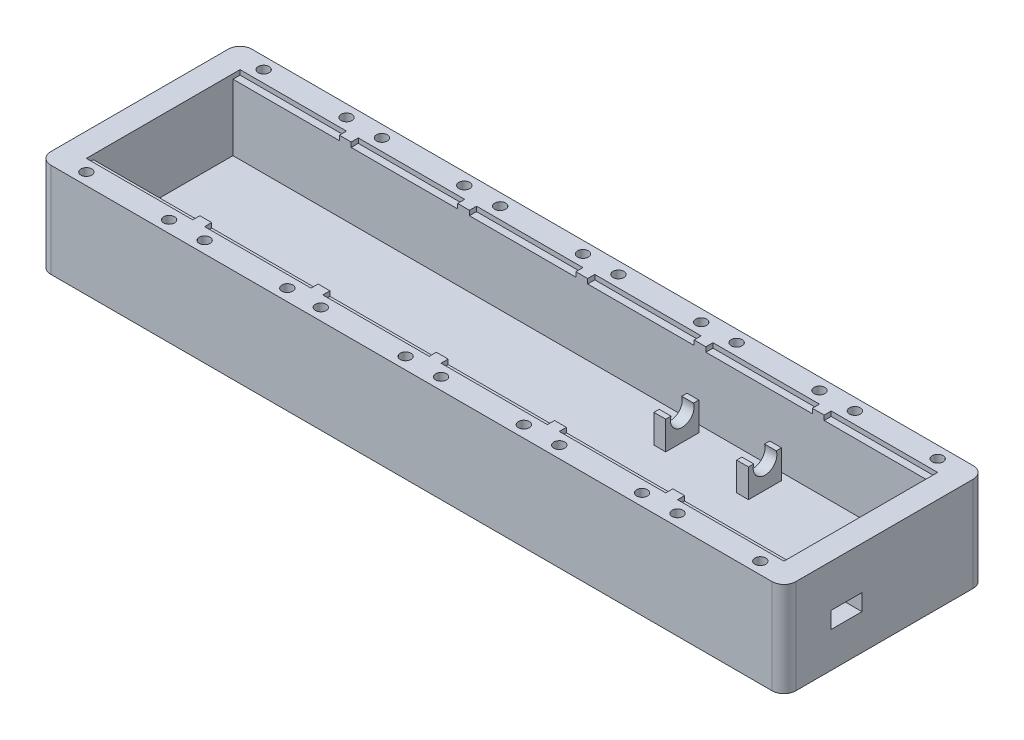
SolidWorks part; units mm, degrees
material "Starkstromplatine"
ref_plane "Ebene vorne" through (0, 0, 0) normal (0, 0, 1) x (1, 0, 0)
ref_plane "Ebene oben" through (0, 0, 0) normal (0, 1, 0) x (1, 0, 0)
ref_plane "Ebene rechts" through (0, 0, 0) normal (1, 0, 0) x (0, 0, -1)
sketch "Skizze2" plane through (0, 0, 0) normal (0, 0, 1) x (1, 0, 0)
  line L1 (0, 0) -> (315, 0)
  line L2 (0, 0) -> (0, 40)
  line L3 (0, 40) -> (315, 40)
  line L4 (315, 0) -> (315, 40)
  dimension "D1" = 315
  dimension "D2" = 40
extrude "Aufsatz-Linear austragen1" add sketch "Skizze2" along normal blind 85
sketch "Skizze4" plane through (0, 40, 0) normal (0, 1, 0) x (1, 0, 0)
  line L1 (10, -13) -> (305, -13)
  line L2 (10, -13) -> (10, -72)
  line L3 (10, -72) -> (305, -72)
  line L4 (305, -13) -> (305, -72)
  line L6 (0, -85) -> (0, 0) construction
  line L7 (315, -85) -> (315, 0) construction
  line L8 (315, -85) -> (0, -85) construction
  dimension "D1" = 59
  dimension "D2" = 13
  dimension "D3" = 10
  dimension "D4" = 10
extrude "Schnitt-Linear austragen1" cut sketch "Skizze4" against normal blind 30
sketch "Skizze11" plane through (0, 40, 0) normal (0, 1, 0) x (1, 0, 0)
  line L0 (10, -72) -> (305, -72) construction
  line L1 (10, -13) -> (55, -13)
  line L2 (10, -13) -> (10, -10)
  line L3 (10, -10) -> (55, -10)
  line L4 (55, -13) -> (55, -10)
  line L5 (55, -72) -> (10, -72)
  line L6 (55, -72) -> (55, -75)
  line L7 (55, -75) -> (10, -75)
  line L8 (10, -72) -> (10, -75)
  line L9 (305, -13) -> (10, -13) construction
  line L10 (60, -75) -> (105, -75)
  line L11 (60, -75) -> (60, -72)
  line L12 (60, -72) -> (105, -72)
  line L13 (105, -75) -> (105, -72)
  line L14 (110, -75.0087) -> (155, -75.0087)
  line L15 (110, -75.0087) -> (110, -72)
  line L16 (110, -72) -> (155, -72)
  line L17 (155, -75.0087) -> (155, -72)
  line L18 (160, -75.0087) -> (205, -75.0087)
  line L19 (160, -75.0087) -> (160, -72)
  line L20 (160, -72) -> (205, -72)
  line L21 (205, -75.0087) -> (205, -72)
  line L22 (210, -75) -> (255, -75)
  line L23 (210, -75) -> (210, -72)
  line L24 (210, -72) -> (255, -72)
  line L25 (255, -75) -> (255, -72)
  line L26 (260, -75) -> (305, -75)
  line L27 (260, -75) -> (260, -72)
  line L28 (260, -72) -> (305, -72)
  line L29 (305, -75) -> (305, -72)
  line L30 (305, -13) -> (260, -13)
  line L31 (305, -13) -> (305, -10)
  line L32 (305, -10) -> (260, -10)
  line L33 (260, -13) -> (260, -10)
  line L35 (255, -13) -> (210, -13)
  line L36 (255, -13) -> (255, -10)
  line L37 (255, -10) -> (210, -10)
  line L38 (210, -13) -> (210, -10)
  line L39 (205, -13) -> (160, -13)
  line L40 (205, -13) -> (205, -10)
  line L41 (205, -10) -> (160, -10)
  line L42 (160, -13) -> (160, -10)
  line L43 (155, -13) -> (110, -13)
  line L44 (155, -13) -> (155, -10)
  line L45 (155, -10) -> (110, -10)
  line L46 (110, -13) -> (110, -10)
  line L47 (105, -13) -> (60, -13)
  line L48 (105, -13) -> (105, -10)
  line L49 (105, -10) -> (60, -10)
  line L50 (60, -13) -> (60, -10)
  dimension "D1" = 45
  dimension "D2" = 3
  dimension "D3" = 45
  dimension "D4" = 5
  dimension "D5" = 5
  dimension "D6" = 5
  dimension "D7" = 5
  dimension "D8" = 5
  dimension "D9" = 5
  dimension "D10" = 45
  dimension "D11" = 45
  dimension "D12" = 45
  dimension "D13" = 45
  dimension "D14" = 45
  dimension "D15" = 5
  dimension "D16" = 5
  dimension "D17" = 5
  dimension "D18" = 5
  dimension "D19" = 45
  dimension "D20" = 45
  dimension "D21" = 45
  dimension "D22" = 45
  dimension "D23" = 3
  dimension "D24" = 3
  dimension "D25" = 3
  dimension "D26" = 3
  dimension "D27" = 3
  dimension "D28" = 3
  dimension "D29" = 3
  dimension "D30" = 3
extrude "Schnitt-Linear austragen4" cut sketch "Skizze11" against normal blind 2
sketch "Skizze17" plane through (0, 40, 0) normal (0, 1, 0) x (1, 0, 0)
  line L0 (55, -75) -> (55, -72) construction
  line L1 (315, 0) -> (0, 0) construction
  line L2 (315, -85) -> (0, -85) construction
  line L3 (10, -72) -> (10, -75) construction
  line L4 (10, -10) -> (10, -75) construction
  line L5 (55, -13) -> (55, -10) construction
  line L6 (60, -72) -> (60, -75) construction
  line L7 (105, -75) -> (105, -72) construction
  line L8 (155, -75.0087) -> (155, -72) construction
  line L10 (160, -72) -> (160, -75.0087) construction
  line L11 (205, -75.0087) -> (205, -72) construction
  line L12 (305, -75) -> (305, -10) construction
  line L13 (260, -72) -> (260, -75) construction
  line L14 (255, -75) -> (255, -72) construction
  line L15 (210, -72) -> (210, -75) construction
  line L16 (60, -10) -> (60, -13) construction
  line L18 (110, -10) -> (110, -13) construction
  circle A0 centre (50, -80) radius 2.3
  circle A1 centre (15, -80) radius 2.3
  circle A2 centre (15, -5) radius 2.3
  circle A3 centre (50, -5) radius 2.3
  circle A4 centre (65, -5) radius 2.3
  circle A5 centre (99.8349, -5) radius 2.3
  circle A6 centre (65, -80) radius 2.3
  circle A7 centre (100, -80) radius 2.3
  circle A8 centre (114.1455, -80) radius 2.3
  circle A9 centre (150, -80) radius 2.3
  circle A10 centre (165, -80) radius 2.3
  circle A11 centre (200, -80) radius 2.3
  circle A12 centre (215, -80) radius 2.3
  circle A13 centre (250, -80) radius 2.3
  circle A14 centre (265, -80) radius 2.3
  circle A15 centre (300, -80) radius 2.3
  circle A16 centre (300, -5) radius 2.3
  circle A17 centre (265, -5) radius 2.3
  circle A18 centre (250, -5) radius 2.3
  circle A19 centre (215, -5) radius 2.3
  circle A20 centre (200, -5) radius 2.3
  circle A21 centre (165, -5) radius 2.3
  circle A22 centre (150, -5) radius 2.3
  circle A23 centre (115, -5) radius 2.3
  dimension "D1" = 4.6
  dimension "D2" = 4.6
  dimension "D3" = 4.6
  dimension "D4" = 4.6
  dimension "D5" = 5
  dimension "D6" = 5
  dimension "D7" = 5
  dimension "D8" = 5
  dimension "D10" = 5
  dimension "D11" = 5
  dimension "D12" = 5
  dimension "D13" = 4.6
  dimension "D14" = 4.6
  dimension "D15" = 4.6
  dimension "D16" = 4.6
  dimension "D17" = 4.6
  dimension "D18" = 4.6
  dimension "D19" = 4.6
  dimension "D20" = 4.6
  dimension "D21" = 4.6
  dimension "D22" = 4.6
  dimension "D23" = 5
  dimension "D25" = 5
  dimension "D26" = 5
  dimension "D27" = 5
  dimension "D28" = 5
  dimension "D29" = 5
  dimension "D30" = 5
  dimension "D31" = 5
  dimension "D32" = 5
  dimension "D33" = 5
  dimension "D34" = 5
  dimension "D35" = 5
  dimension "D36" = 5
  dimension "D37" = 5
  dimension "D38" = 5
  dimension "D39" = 5
  dimension "D40" = 5
  dimension "D41" = 5
  dimension "D42" = 5
  dimension "D43" = 4.6
  dimension "D44" = 4.6
  dimension "D45" = 4.6
  dimension "D46" = 4.6
  dimension "D47" = 4.6
  dimension "D48" = 4.6
  dimension "D49" = 4.6
  dimension "D50" = 4.6
  dimension "D51" = 4.6
  dimension "D52" = 4.6
  dimension "D53" = 5
  dimension "D54" = 5
  dimension "D55" = 5
  dimension "D9" = 5
  dimension "D24" = 5
extrude "Schnitt-Linear austragen6" cut sketch "Skizze17" against normal blind 4
fillet "Verrundung2" radius 5 1 edges at (0, 20, 85)
fillet "Verrundung3" radius 5 1 edges at (0, 20, 0)
fillet "Verrundung4" radius 5 1 edges at (315, 20, 0)
fillet "Verrundung6" radius 5 1 edges at (315, 20, 85)
sketch "Skizze18" plane through (305, 0, 0) normal (-1, 0, 0) x (0, 0, 1)
  line L0 (72, 10) -> (72, 38) construction
  line L1 (52, 22) -> (65, 22)
  line L2 (52, 22) -> (52, 15)
  line L3 (52, 15) -> (65, 15)
  line L4 (65, 22) -> (65, 15)
  line L5 (72, 10) -> (13, 10) construction
  dimension "D1" = 7
  dimension "D2" = 13
  dimension "D3" = 7
  dimension "D4" = 5
extrude "Schnitt-Linear austragen7" cut sketch "Skizze18" against normal blind 10
sketch "Skizze20" plane through (0, 10, 0) normal (0, 1, 0) x (1, 0, 0)
  line L0 (305, -13) -> (10, -13) construction
  line L1 (240, -16) -> (245, -16)
  line L2 (240, -16) -> (240, -30)
  line L3 (240, -30) -> (245, -30)
  line L4 (245, -16) -> (245, -30)
  line L5 (205, -16) -> (210, -16)
  line L6 (205, -16) -> (205, -30)
  line L7 (205, -30) -> (210, -30)
  line L8 (210, -16) -> (210, -30)
  line L9 (305, -72) -> (305, -13) construction
  dimension "D1" = 14
  dimension "D2" = 14
  dimension "D3" = 5
  dimension "D4" = 5
  dimension "D5" = 3
  dimension "D6" = 3
  dimension "D7" = 30
  dimension "D8" = 60
extrude "Aufsatz-Linear austragen2" add sketch "Skizze20" along normal blind 12
sketch "Skizze21" plane through (205, 0, 0) normal (-1, 0, 0) x (0, 0, 1)
  line L0 (16, 22) -> (16, 10) construction
  line L1 (16, 22) -> (30, 22) construction
  circle A0 centre (23, 20.5) radius 5
  dimension "D1" = 7
  dimension "D2" = 1.5
extrude "Schnitt-Linear austragen8" cut sketch "Skizze21" against normal blind 71
